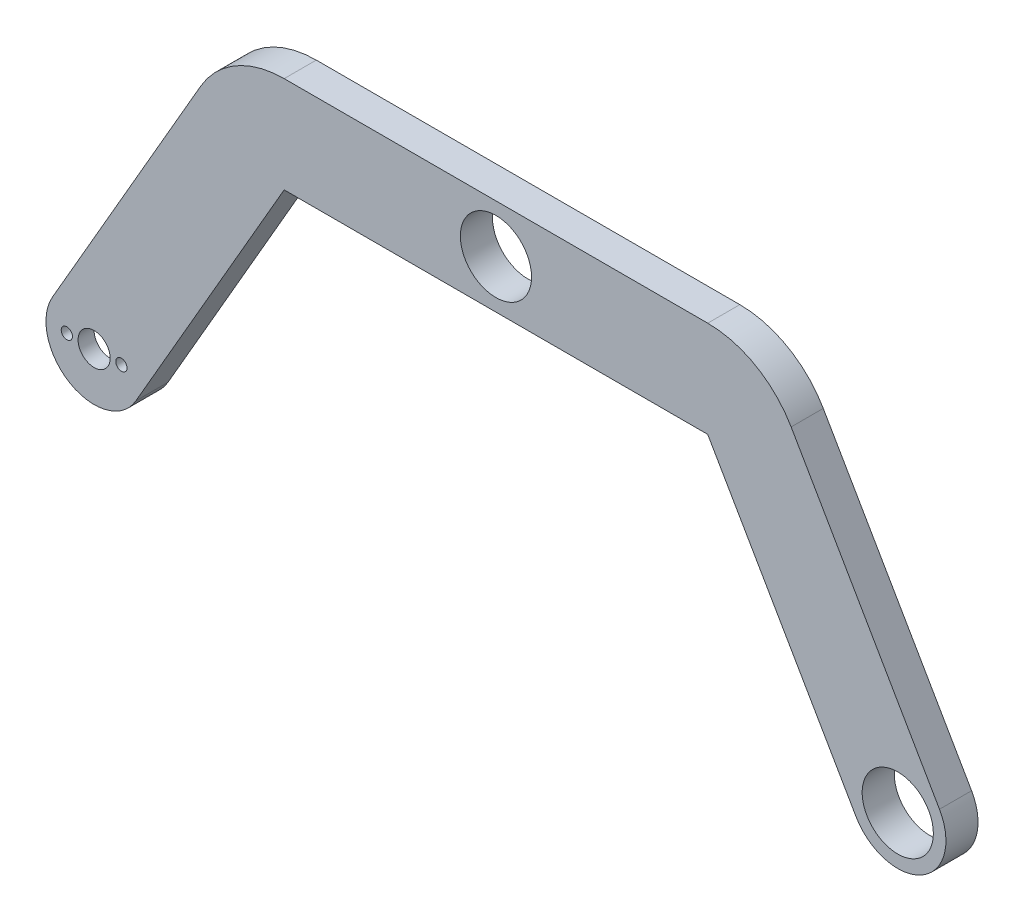
SolidWorks part; units mm, degrees
ref_plane "Front Plane" through (0, 0, 0) normal (0, 0, 1) x (1, 0, 0)
ref_plane "Top Plane" through (0, 0, 0) normal (0, 1, 0) x (1, 0, 0)
ref_plane "Right Plane" through (0, 0, 0) normal (1, 0, 0) x (0, 0, -1)
sketch "Sketch1" plane through (0, 0, 0) normal (0, 0, 1) x (1, 0, 0)
  line L0 (0, -15) -> (0, 15) construction
  line L1 (65.9559, 15) -> (-65.9559, 15)
  line L2 (65.9559, -15) -> (-65.9559, -15)
  line L3 (-65.9559, -15) -> (-112.1545, -95.0183)
  line L5 (-138.1353, -80.0183) -> (-91.9367, 0)
  line L6 (138.1353, -80.0183) -> (91.9367, 0)
  line L8 (65.9559, -15) -> (112.1545, -95.0183)
  arc A1 (-91.9367, 0) -> (-65.9559, 15) centre (-65.9559, -15) cw
  arc A2 (91.9367, 0) -> (65.9559, 15) centre (65.9559, -15) ccw
  circle A3 centre (-125.1449, -87.5183) radius 15 construction
  arc A5 (-138.1353, -80.0183) -> (-112.1545, -95.0183) centre (-125.1449, -87.5183) ccw
  arc A6 (112.1545, -95.0183) -> (138.1353, -80.0183) centre (125.1449, -87.5183) ccw
  circle A7 centre (-133.6449, -87.5183) radius 1.75
  circle A8 centre (-116.6449, -87.5183) radius 1.75
  point P4 (0, 0)
  point P6 (0, 15)
  point P10 (0, -15)
  dimension "D2" = 3.5
  dimension "D4" = 3.5
  dimension "D1" = 30
  dimension "D3" = 120
extrude "Boss-Extrude1" add sketch "Sketch1" along normal blind 10
sketch "Sketch2" plane through (0, 0, 10) normal (0, 0, 1) x (1, 0, 0)
  circle A0 centre (0, 0) radius 11.0875
  circle A1 centre (-125.1449, -87.5183) radius 5
  circle A2 centre (125.1449, -87.5183) radius 11.0875
  dimension "D1" = 22.175
  dimension "D2" = 22.175
extrude "Cut-Extrude1" cut sketch "Sketch2" against normal up to surface (10 mm away) up to face at (-131.8949, -87.5183, 0)
sketch "Sketch3" plane through (0, 0, 0) normal (0, 0, -1) x (-1, 0, 0)
  circle A0 centre (0, 0) radius 12
sketch "Sketch4" plane through (0, 0, 0) normal (0, 0, -1) x (-1, 0, 0)
  circle A0 centre (125.1449, -87.5183) radius 13
  dimension "D1" = 26
extrude "Cut-Extrude2" cut sketch "Sketch4" against normal offset from surface (5 mm away) 5 up to face at (11.0875, 0, 10)
sketch "Sketch5" plane through (0, 0, 10) normal (0, 0, 1) x (1, 0, 0)
  circle A0 centre (0, 0) radius 3.5
  dimension "D1" = 7
